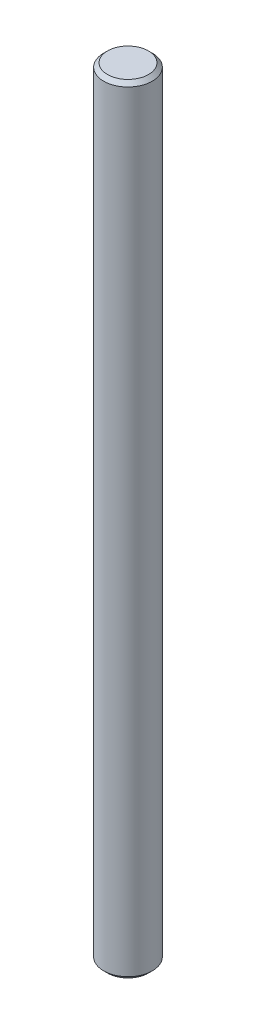
SolidWorks part; units mm, degrees
ref_plane "Front Plane" through (0, 0, 0) normal (0, 0, 1) x (1, 0, 0)
ref_plane "Top Plane" through (0, 0, 0) normal (0, 1, 0) x (1, 0, 0)
ref_plane "Right Plane" through (0, 0, 0) normal (1, 0, 0) x (0, 0, -1)
sketch "Bar face" plane through (0, 0, 0) normal (0, 1, 0) x (1, 0, 0)
  circle A0 centre (0, 0) radius 3.175
  dimension "D1" = 6.35
extrude "Bar extrude" add sketch "Bar face" along normal blind 101.6
chamfer "Chamfer2" distance 0.5 2 edges at (0, 101.6, 3.175) (0, 0, 3.175) tangent propagation no
